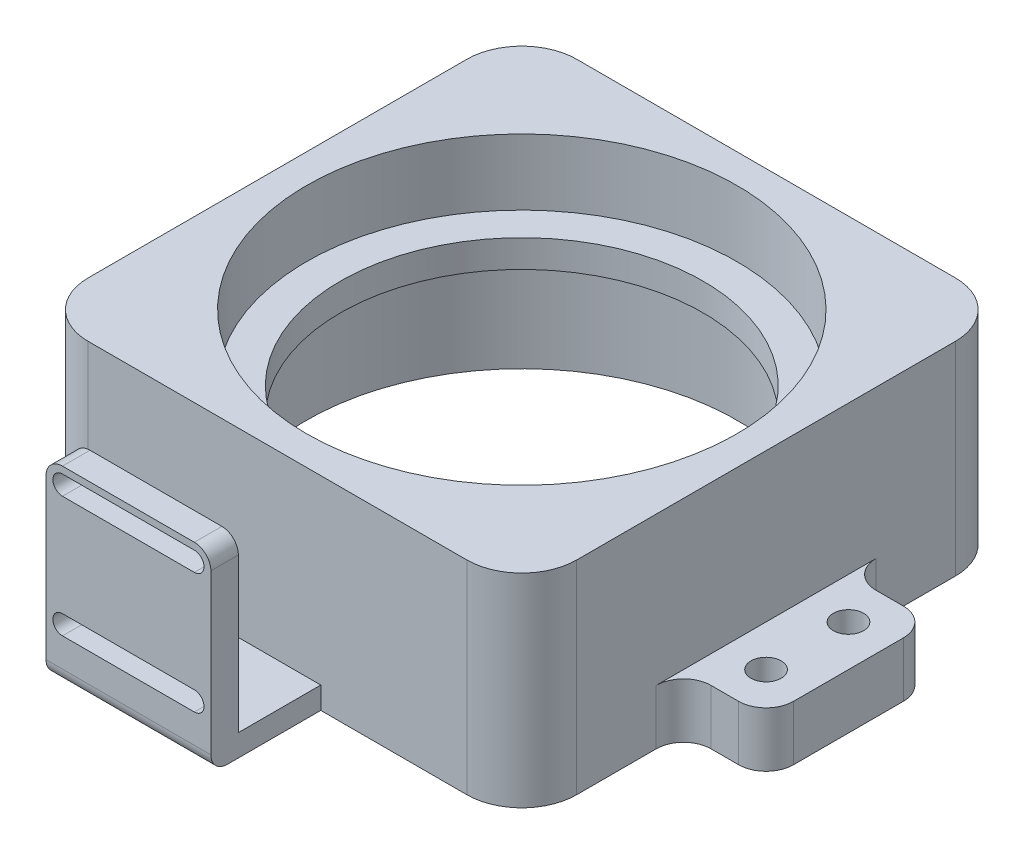
SolidWorks part; units mm, degrees
ref_plane "Front Plane" through (0, 0, 0) normal (0, 0, 1) x (1, 0, 0)
ref_plane "Top Plane" through (0, 0, 0) normal (0, 1, 0) x (1, 0, 0)
ref_plane "Right Plane" through (0, 0, 0) normal (1, 0, 0) x (0, 0, -1)
sketch "Sketch1" plane through (0, 0, 0) normal (0, 1, 0) x (1, 0, 0)
  line L1 (0, 0) -> (88.9, 0)
  line L2 (0, 0) -> (0, 88.9)
  line L3 (0, 88.9) -> (88.9, 88.9)
  line L4 (88.9, 0) -> (88.9, 88.9)
  circle A0 centre (44.45, 44.45) radius 29.88
  circle A1 centre (44.45, 44.45) radius 39.15
  dimension "D1" = 88.9
  dimension "D2" = 88.9
extrude "Boss-Extrude1" add sketch "Sketch1" along normal blind 20 contours L1 L4 L3 L2 A1 region at (1.2572, 0, -44.45)
sketch "Sketch2" plane through (0, 20, 0) normal (0, 1, 0) x (1, 0, 0)
  line L1 (0, 88.9) -> (88.9, 88.9)
  line L2 (0, 88.9) -> (0, 0)
  line L3 (0, 0) -> (88.9, 0)
  line L4 (88.9, 88.9) -> (88.9, 0)
  circle A0 centre (44.45, 44.45) radius 33
extrude "Boss-Extrude3" add sketch "Sketch2" along normal blind 5
sketch "Sketch3" plane through (0, 25, 0) normal (0, 1, 0) x (1, 0, 0)
  line L1 (0, 0) -> (88.9, 0)
  line L2 (0, 0) -> (0, 88.9)
  line L3 (0, 88.9) -> (88.9, 88.9)
  line L4 (88.9, 0) -> (88.9, 88.9)
  circle A0 centre (44.45, 44.45) radius 39.15
extrude "Boss-Extrude4" add sketch "Sketch3" along normal blind 12
sketch "Sketch4" plane through (0, 0, 0) normal (0, -1, 0) x (1, 0, 0)
  line L0 (0, 0) -> (0, -88.9) construction
  line L1 (0, -44.45) -> (-15, -44.45)
  line L2 (0, -44.45) -> (0, -29.45)
  line L3 (0, -29.45) -> (-15, -29.45)
  line L4 (-15, -44.45) -> (-15, -29.45)
  line L5 (88.9, 0) -> (88.9, -88.9) construction
  line L6 (0, -44.45) -> (-15, -44.45)
  line L7 (0, -44.45) -> (0, -59.45)
  line L8 (0, -59.45) -> (-15, -59.45)
  line L9 (-15, -44.45) -> (-15, -59.45)
  line L10 (88.9, -44.45) -> (103.9, -44.45)
  line L11 (88.9, -44.45) -> (88.9, -29.45)
  line L12 (88.9, -29.45) -> (103.9, -29.45)
  line L13 (103.9, -44.45) -> (103.9, -29.45)
  line L15 (88.9, -44.45) -> (103.9, -44.45)
  line L16 (88.9, -44.45) -> (88.9, -59.45)
  line L17 (88.9, -59.45) -> (103.9, -59.45)
  line L18 (103.9, -44.45) -> (103.9, -59.45)
  circle A0 centre (-7.5, -36.95) radius 2.75
  circle A1 centre (-7.5, -51.95) radius 2.75
  circle A2 centre (96.4, -36.95) radius 2.75
  circle A3 centre (96.4, -51.95) radius 2.75
  line M10 (0, 0) -> (0, -88.9)
  line M12 (88.9, -88.9) -> (88.9, 0)
  dimension "D1" = 15
  dimension "D2" = 15
  dimension "D3" = 15
  dimension "D4" = 15
  dimension "D5" = 15
  dimension "D6" = 15
  dimension "D7" = 15
extrude "Boss-Extrude5" add sketch "Sketch4" against normal blind 10 contours L4 L1 L3 A0 M10 | L1 L9 L8 A1 M10 | L10 L13 L12 A2 M12 | L18 L10 L17 A3 M12 region at (-0.2121, 0, -51.95) region at (-7.5, 0, -44.2379) region at (89.1121, 0, -36.95) region at (96.4, 0, -44.6621)
fillet "Fillet1" radius 5 8 edges at (88.9, 5, -59.45) (103.9, 5, -59.45) (103.9, 5, -29.45) (88.9, 5, -29.45) (-15, 5, -59.45) (0, 5, -59.45) (-15, 5, -29.45) (0, 5, -29.45)
fillet "Fillet2" radius 10 4 edges at (0, 18.5, 0) (88.9, 18.5, 0) (88.9, 18.5, -88.9) (0, 18.5, -88.9)
sketch "Sketch5" plane through (0, 0, 0) normal (0, 0, 1) x (1, 0, 0)
  line L0 (10, 0) -> (78.9, 0) construction
  line L1 (52.325, 0) -> (22.325, 0)
  line L2 (52.325, 0) -> (52.325, 4)
  line L3 (52.325, 4) -> (22.325, 4)
  line L4 (22.325, 0) -> (22.325, 4)
  dimension "D1" = 4
  dimension "D2" = 30
extrude "Boss-Extrude6" add sketch "Sketch5" along normal blind 15
sketch "Sketch6" plane through (0, 0, 15) normal (0, 0, 1) x (1, 0, 0)
  line L1 (22.325, 0) -> (52.325, 0)
  line L2 (22.325, 0) -> (22.325, 35)
  line L3 (22.325, 35) -> (52.325, 35)
  line L4 (52.325, 0) -> (52.325, 35)
  line L6 (25.325, 33.75) -> (49.325, 33.75)
  line L7 (25.325, 30.25) -> (49.325, 30.25)
  line L8 (25.325, 11.75) -> (49.325, 11.75)
  line L9 (49.325, 8.25) -> (25.325, 8.25)
  circle A1 centre (25.325, 32) radius 1.75
  circle A2 centre (49.325, 32) radius 1.75
  circle A3 centre (25.325, 10) radius 1.75
  circle A4 centre (49.325, 10) radius 1.75
  line M1 (52.325, 0) -> (52.325, 4)
  line M2 (52.325, 4) -> (22.325, 4)
  line M3 (22.325, 4) -> (22.325, 0)
  line M4 (22.325, 0) -> (52.325, 0)
  dimension "D2" = 3
  dimension "D4" = 3
  dimension "D6" = 22
  dimension "D7" = 3
  dimension "D1" = 35
  dimension "D3" = 3
  dimension "D5" = 3
  dimension "D8" = 3
extrude "Boss-Extrude7" add sketch "Sketch6" along normal blind 5 contours L4 L3 L2 A4 L9 A3 L8 A2 L7 A1 L6 M2 | M4 M1 M2 M3 region at (37.325, 2, 15) region at (37.325, 19.1219, 15)
fillet "Fillet3" radius 3 3 edges at (37.325, 0, 20) (22.325, 35, 17.5) (52.325, 35, 17.5)
